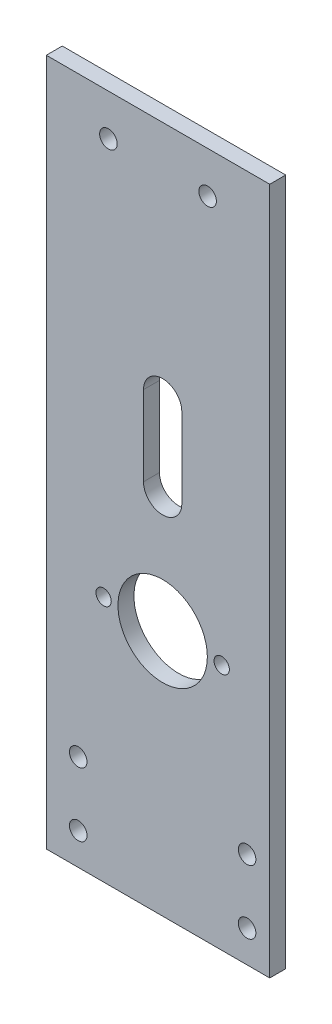
SolidWorks part; units mm, degrees
ref_plane "Front Plane" through (0, 0, 0) normal (0, 0, 1) x (1, 0, 0)
ref_plane "Top Plane" through (0, 0, 0) normal (0, 1, 0) x (1, 0, 0)
ref_plane "Right Plane" through (0, 0, 0) normal (1, 0, 0) x (0, 0, -1)
sketch "Sketch1" plane through (0, 0, 0) normal (0, 0, 1) x (1, 0, 0)
  line L0 (-26.4505, -10) -> (26.4505, 10) construction
  line L2 (-36.4505, -77.3566) -> (-36.4505, 77.3566)
  line L3 (-36.4505, 77.3566) -> (33.5495, 77.3566)
  line L4 (33.5495, -77.3566) -> (33.5495, 77.3566)
  line L5 (-26.4505, 10) -> (26.4505, -10) construction
  line L6 (-36.4505, -77.3566) -> (33.5495, -77.3566)
  line L7 (-18.5, 57.3566) -> (18.5, 57.3566) construction
  line L8 (-15.5, -33.6434) -> (-15.5, -40.6434) construction
  line L9 (-15.5, -68.1434) -> (15.5, -68.1434) construction
  line L11 (-15.5, -68.1434) -> (-15.5, -37.1434) construction
  line L14 (-15.5, -37.1434) -> (15.5, -37.1434) construction
  line L15 (15.5, -68.1434) -> (15.5, -37.1434) construction
  line L16 (-15.5, -68.1434) -> (15.5, -37.1434) construction
  line L17 (-15.5, -37.1434) -> (15.5, -68.1434) construction
  line L18 (-13.95, -33.6434) -> (-13.95, -40.6434)
  line L19 (-17.05, -33.6434) -> (-17.05, -40.6434)
  line L20 (15.5, -33.6434) -> (15.5, -40.6434) construction
  line L21 (17.05, -33.6434) -> (17.05, -40.6434)
  line L22 (13.95, -33.6434) -> (13.95, -40.6434)
  line L23 (15.5, -64.6434) -> (15.5, -71.6434) construction
  line L24 (17.05, -64.6434) -> (17.05, -71.6434)
  line L25 (13.95, -64.6434) -> (13.95, -71.6434)
  line L26 (-15.5, -64.6434) -> (-15.5, -71.6434) construction
  line L27 (-13.95, -64.6434) -> (-13.95, -71.6434)
  line L28 (-17.05, -64.6434) -> (-17.05, -71.6434)
  line L29 (0, -56.1434) -> (0, -49.1434) construction
  line L30 (-12, -56.1434) -> (-12, -49.1434)
  line L31 (12, -56.1434) -> (12, -49.1434)
  line L33 (-36.4505, 77.3566) -> (33.5495, 77.3566)
  line L34 (-36.4505, 77.3566) -> (-36.4505, 195.3566)
  line L35 (-36.4505, 195.3566) -> (33.5495, 195.3566)
  line L36 (33.5495, 77.3566) -> (33.5495, 195.3566)
  line L38 (0, 119.8566) -> (0, 94.8566) construction
  line L39 (6, 119.8566) -> (6, 94.8566)
  line L40 (-6, 119.8566) -> (-6, 94.8566)
  circle A0 centre (-18.5, 57.3566) radius 2.4
  circle A1 centre (18.5, 57.3566) radius 2.4
  circle A2 centre (0, 57.3566) radius 5
  circle A3 centre (-26.4505, 10) radius 2.75
  circle A4 centre (26.4505, 10) radius 2.75
  circle A5 centre (26.4505, -10) radius 2.75
  circle A6 centre (-26.4505, -10) radius 2.75
  circle A7 centre (0, 57.3566) radius 14
  arc A13 (-13.95, -33.6434) -> (-17.05, -33.6434) centre (-15.5, -33.6434) ccw
  arc A14 (-17.05, -40.6434) -> (-13.95, -40.6434) centre (-15.5, -40.6434) ccw
  arc A15 (17.05, -33.6434) -> (13.95, -33.6434) centre (15.5, -33.6434) ccw
  arc A16 (13.95, -40.6434) -> (17.05, -40.6434) centre (15.5, -40.6434) ccw
  arc A17 (17.05, -64.6434) -> (13.95, -64.6434) centre (15.5, -64.6434) ccw
  arc A18 (13.95, -71.6434) -> (17.05, -71.6434) centre (15.5, -71.6434) ccw
  arc A19 (-13.95, -64.6434) -> (-17.05, -64.6434) centre (-15.5, -64.6434) ccw
  arc A20 (-17.05, -71.6434) -> (-13.95, -71.6434) centre (-15.5, -71.6434) ccw
  arc A21 (-12, -56.1434) -> (12, -56.1434) centre (0, -56.1434) ccw
  arc A22 (12, -49.1434) -> (-12, -49.1434) centre (0, -49.1434) ccw
  arc A23 (6, 119.8566) -> (-6, 119.8566) centre (0, 119.8566) ccw
  arc A24 (-6, 94.8566) -> (6, 94.8566) centre (0, 94.8566) ccw
  circle A25 centre (-16.9918, 182.3877) radius 2.75
  circle A26 centre (14.0909, 182.3877) radius 2.75
  point P0 (0, 0)
  point P5 (-36.4505, 0)
  point P6 (0, -52.6434)
  point P25 (-15.5, -37.1434)
  point P38 (15.5, -37.1434)
  point P45 (15.5, -68.1434)
  point P52 (-15.5, -68.1434)
  point P57 (0, -52.6434)
  point P64 (0, 107.3566)
  point P67 (0, 107.3566)
  point P78 (0, 0)
  point P79 (0, 0)
  point P80 (0, 0)
  dimension "D4" = 4.8
  dimension "D5" = 10
  dimension "D6" = 5.5
  dimension "D11" = 28
  dimension "D7" = 12
  dimension "D12" = 1.55
  dimension "D17" = 6
  dimension "D20" = 5.5
  dimension "D1" = 70
  dimension "D2" = 31
  dimension "D3" = 37
  dimension "D8" = 20
  dimension "D9" = 7
  dimension "D10" = 20
  dimension "D13" = 110
  dimension "D14" = 7
  dimension "D15" = 50
  dimension "D16" = 138
  dimension "D18" = 25
  dimension "D19" = 12.9688
extrude "Boss-Extrude1" add sketch "Sketch1" along normal blind 5 contours L2 L6 L4 L3 A7 A6 A5 A4 A3 A1 A0 region at (-1.6809, 0.1525, 0)
extrude "Boss-Extrude2" add sketch "Sketch1<4>" along normal blind 5 contours L3 L36 L35 L34 A24 L40 A23 L39 region at (-1.5273, 137.6121, 0)
sketch "Sketch1<4>" plane through (0, 0, 0) normal (0, 0, 1) x (1, 0, 0) same geometry as "Sketch1"
sketch "Sketch2" plane through (0, 0, 5) normal (0, 0, 1) x (1, 0, 0)
  line L0 (-36.4505, -20) -> (33.5495, -20)
  line L4 (-36.4505, 195.3566) -> (-36.4505, -77.3566)
  line L5 (-36.4505, -77.3566) -> (33.5495, -77.3566)
  line L6 (33.5495, -77.3566) -> (33.5495, 195.3566)
  line L7 (33.5495, 195.3566) -> (-36.4505, 195.3566)
  line L8 (-36.4505, 195.3566) -> (-36.4505, -77.3566)
  line L9 (-36.4505, -77.3566) -> (33.5495, -77.3566)
  line L10 (33.5495, -77.3566) -> (33.5495, 195.3566)
  line L11 (33.5495, 195.3566) -> (-36.4505, 195.3566)
  circle A0 centre (26.4505, -10) radius 2.75 construction
  circle A1 centre (26.4505, -10) radius 2.75
  arc M6 (-12, -49.1434) -> (12, -49.1434) centre (0, -49.1434) cw
  line M7 (12, -49.1434) -> (12, -56.1434)
  arc M8 (12, -56.1434) -> (-12, -56.1434) centre (0, -56.1434) cw
  line M9 (-12, -56.1434) -> (-12, -49.1434)
  arc M10 (-13.95, -71.6434) -> (-17.05, -71.6434) centre (-15.5, -71.6434) cw
  line M11 (-17.05, -71.6434) -> (-17.05, -64.6434)
  arc M12 (-17.05, -64.6434) -> (-13.95, -64.6434) centre (-15.5, -64.6434) cw
  line M13 (-13.95, -64.6434) -> (-13.95, -71.6434)
  arc M14 (17.05, -71.6434) -> (13.95, -71.6434) centre (15.5, -71.6434) cw
  line M15 (13.95, -71.6434) -> (13.95, -64.6434)
  arc M16 (13.95, -64.6434) -> (17.05, -64.6434) centre (15.5, -64.6434) cw
  line M17 (17.05, -64.6434) -> (17.05, -71.6434)
  arc M18 (17.05, -40.6434) -> (13.95, -40.6434) centre (15.5, -40.6434) cw
  line M19 (13.95, -40.6434) -> (13.95, -33.6434)
  arc M20 (13.95, -33.6434) -> (17.05, -33.6434) centre (15.5, -33.6434) cw
  line M21 (17.05, -33.6434) -> (17.05, -40.6434)
  arc M22 (-13.95, -40.6434) -> (-17.05, -40.6434) centre (-15.5, -40.6434) cw
  line M23 (-17.05, -40.6434) -> (-17.05, -33.6434)
  arc M24 (-17.05, -33.6434) -> (-13.95, -33.6434) centre (-15.5, -33.6434) cw
  line M25 (-13.95, -33.6434) -> (-13.95, -40.6434)
  line M33 (-36.4505, 195.3566) -> (-36.4505, -77.3566)
  line M34 (-36.4505, -77.3566) -> (33.5495, -77.3566)
  line M35 (33.5495, -77.3566) -> (33.5495, 195.3566)
  dimension "D2" = 10
  dimension "D1" = 0
extrude "Cut-Extrude1" cut sketch "Sketch2" against normal blind 10 contours L0 M33 M34 M35 M25 M22 M23 M24 M21 M18 M19 M20 M17 M14 M15 M16 M13 M10 M11 M12 M9 M6 M7 M8 region at (-1.4505, -20.905, 5)
